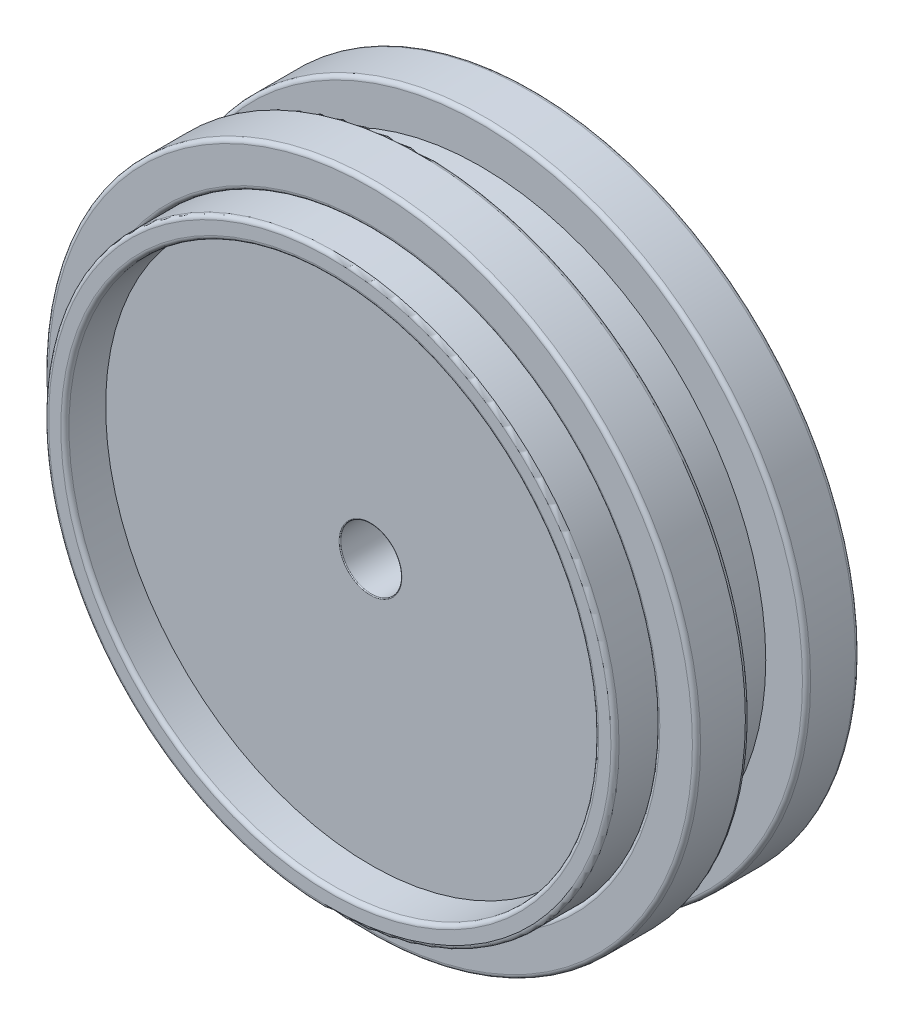
SolidWorks part; units mm, degrees
ref_plane "Front Plane" through (0, 0, 0) normal (0, 0, 1) x (1, 0, 0)
ref_plane "Top Plane" through (0, 0, 0) normal (0, 1, 0) x (1, 0, 0)
ref_plane "Right Plane" through (0, 0, 0) normal (1, 0, 0) x (0, 0, -1)
sketch "Sketch1" plane through (0, 0, 0) normal (0, 0, 1) x (1, 0, 0)
  circle A0 centre (0, 0) radius 82.55
  circle A1 centre (0, 0) radius 88.9
  circle A2 centre (0, 0) radius 101.6
  dimension "D1" = 165.1
  dimension "D2" = 177.8
  dimension "D3" = 203.2
extrude "Boss-Extrude1" add sketch "Sketch1" along normal blind 12.7 and the other way blind 50.8 contours A1 A0 region at (-86.3855, 0, 0)
extrude "Boss-Extrude2" add sketch "Sketch1<3>" against normal blind 50.8 separate body contours A2 A1 region at (-98.7263, 0, 0)
sketch "Sketch1<3>" plane through (0, 0, 0) normal (0, 0, 1) x (1, 0, 0) same geometry as "Sketch1"
extrude "Boss-Extrude3" add sketch "Sketch1<4>" against normal blind 25.4 separate body contours A0 region at (0, 0, 0)
sketch "Sketch1<4>" plane through (0, 0, 0) normal (0, 0, 1) x (1, 0, 0) same geometry as "Sketch1"
sketch "Sketch4" plane through (0, 0, 0) normal (0, 1, 0) x (1, 0, 0)
  line L0 (101.6, 25.4) -> (-112.628, 25.4) construction
  line L1 (101.6, 0) -> (101.6, 50.8) construction
  line L2 (101.6, 34.29) -> (88.9, 34.29)
  line L3 (88.9, 34.29) -> (88.9, 16.51)
  line L4 (88.9, 16.51) -> (101.6, 16.51)
  line L5 (101.6, 16.51) -> (101.6, 34.29)
  line L7 (0, 0) -> (0, -160.0116) construction
  dimension "D1" = 17.78
  dimension "D3" = 12.7
revolve "Cut-Revolve1" cut sketch "Sketch4" angle 360 about L7
sketch "Sketch5" plane through (0, 0, 0) normal (0, 0, 1) x (1, 0, 0)
  circle A0 centre (0, 0) radius 9.525
  dimension "D1" = 19.05
extrude "Cut-Extrude1" cut sketch "Sketch5" against normal blind 44.45
fillet "Fillet1" radius 1.27 3 edges at (88.9, 0, 0) (-101.6, 0, -16.51) (101.6, 0, 0)
fillet "Fillet2" radius 1.27 3 edges at (82.55, 0, -50.8) (82.55, 0, 12.7) (88.9, 0, 12.7)
fillet "Fillet6" radius 1.27 2 edges at (101.6, 0, -50.8) (-101.6, 0, -34.29)
fillet "Fillet9" radius 0.254 2 edges at (9.525, 0, -25.4) (9.525, 0, 0)
